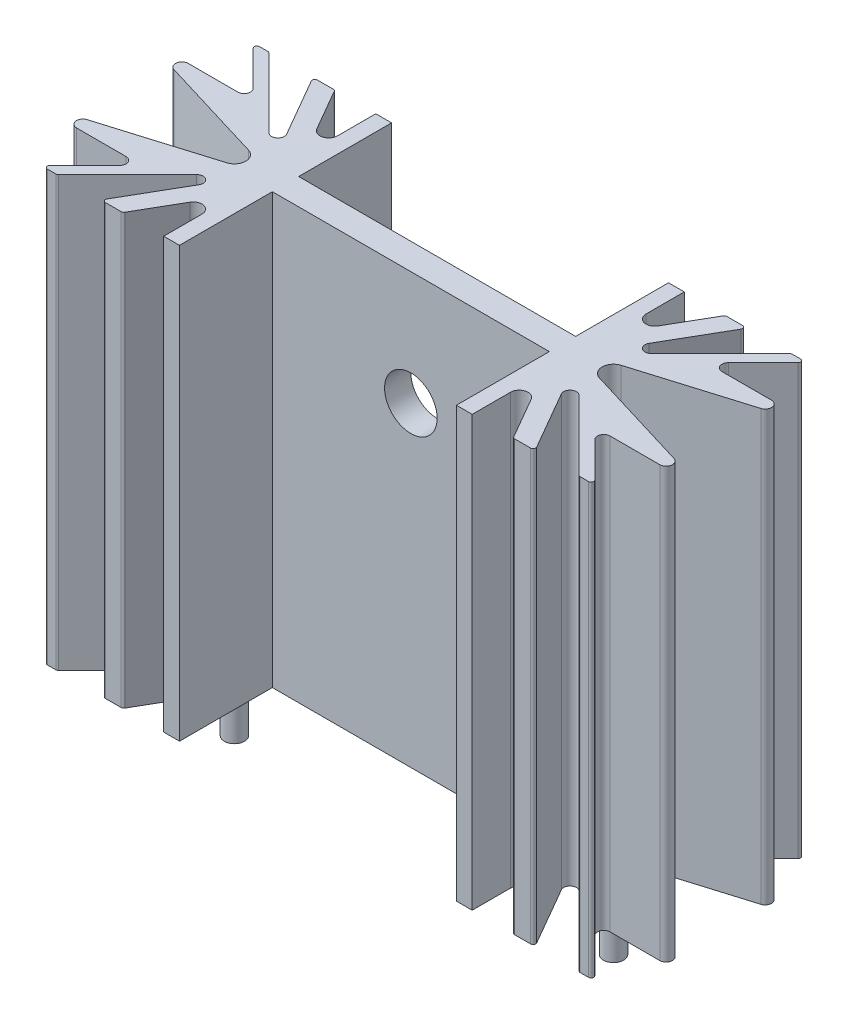
SolidWorks part; units mm, degrees
ref_plane "Front Plane" through (0, 0, 0) normal (0, 0, 1) x (1, 0, 0)
ref_plane "Top Plane" through (0, 0, 0) normal (0, 1, 0) x (1, 0, 0)
ref_plane "Right Plane" through (0, 0, 0) normal (1, 0, 0) x (0, 0, -1)
sketch "Sketch2" plane through (0, 0, 0) normal (0, 1, 0) x (1, 0, 0)
  line L0 (0, 16.6412) -> (0, -12.8924) construction
  line L1 (-22.8588, 0) -> (21.9444, 0) construction
  line L2 (-7.9, -0.75) -> (7.9, -0.75)
  line L3 (7.9, -0.75) -> (7.9, -6.05)
  line L4 (-7.9, -0.75) -> (-7.9, -6.05)
  line L5 (7.9, -6.05) -> (8.8, -6.05)
  line L6 (8.8, -6.05) -> (8.8, -3.866)
  line L7 (9.733, -3.616) -> (11.095, -5.975)
  line L8 (11.2249, -6.05) -> (12.1249, -6.05)
  line L9 (12.2548, -5.825) -> (10.3351, -2.5)
  line L10 (10.9063, -2.0617) -> (14.8507, -6.0061)
  line L11 (14.9568, -6.05) -> (15.4325, -6.05)
  line L12 (15.5386, -5.7939) -> (13.5509, -3.8063)
  line L13 (13.8077, -3.1864) -> (16.6369, -3.1864)
  line L14 (17, -2.8233) -> (17, -6.05) construction
  line L15 (16.7422, -2.4757) -> (10.625, -0.6221)
  line L16 (-7.9, -6.05) -> (-8.8, -6.05)
  line L17 (-8.8, -6.05) -> (-8.8, -3.866)
  line L18 (-9.733, -3.616) -> (-11.095, -5.975)
  line L19 (-11.2249, -6.05) -> (-12.1249, -6.05)
  line L20 (-12.2548, -5.825) -> (-10.3351, -2.5)
  line L21 (-10.9063, -2.0617) -> (-14.8507, -6.0061)
  line L22 (-14.9568, -6.05) -> (-15.4325, -6.05)
  line L23 (-15.5386, -5.7939) -> (-13.5509, -3.8063)
  line L24 (-13.8077, -3.1864) -> (-16.6369, -3.1864)
  line L25 (-16.7422, -2.4757) -> (-10.625, -0.6221)
  line L26 (17, 2.8233) -> (17, 6.05) construction
  line L27 (0, -16.6412) -> (0, 12.8924) construction
  line L28 (-16.7422, 2.4757) -> (-10.625, 0.6221)
  line L29 (-13.8077, 3.1864) -> (-16.6369, 3.1864)
  line L30 (-15.5386, 5.7939) -> (-13.5509, 3.8063)
  line L31 (-14.9568, 6.05) -> (-15.4325, 6.05)
  line L32 (-10.9063, 2.0617) -> (-14.8507, 6.0061)
  line L33 (-12.2548, 5.825) -> (-10.3351, 2.5)
  line L34 (-11.2249, 6.05) -> (-12.1249, 6.05)
  line L35 (-9.733, 3.616) -> (-11.095, 5.975)
  line L36 (-8.8, 6.05) -> (-8.8, 3.866)
  line L37 (-7.9, 6.05) -> (-8.8, 6.05)
  line L38 (16.7422, 2.4757) -> (10.625, 0.6221)
  line L39 (13.8077, 3.1864) -> (16.6369, 3.1864)
  line L40 (15.5386, 5.7939) -> (13.5509, 3.8063)
  line L41 (14.9568, 6.05) -> (15.4325, 6.05)
  line L42 (10.9063, 2.0617) -> (14.8507, 6.0061)
  line L43 (12.2548, 5.825) -> (10.3351, 2.5)
  line L44 (11.2249, 6.05) -> (12.1249, 6.05)
  line L45 (9.733, 3.616) -> (11.095, 5.975)
  line L46 (8.8, 6.05) -> (8.8, 3.866)
  line L47 (7.9, 6.05) -> (8.8, 6.05)
  line L48 (-7.9, 0.75) -> (-7.9, 6.05)
  line L49 (7.9, 0.75) -> (7.9, 6.05)
  line L50 (-7.9, 0.75) -> (7.9, 0.75)
  arc A0 (10.625, -0.6221) -> (10.625, 0.6221) centre (10.8135, 0) cw
  arc A1 (10.3351, -2.5) -> (10.9063, -2.0617) centre (10.6496, -2.3184) cw
  arc A2 (11.095, -5.975) -> (11.2249, -6.05) centre (11.2249, -5.9) ccw
  arc A3 (16.7422, -2.4757) -> (16.6369, -3.1864) centre (16.6369, -2.8233) cw
  arc A4 (13.8077, -3.1864) -> (13.5509, -3.8063) centre (13.8077, -3.5495) ccw
  arc A5 (9.733, -3.616) -> (8.8, -3.866) centre (9.3, -3.866) ccw
  arc A6 (12.1249, -6.05) -> (12.2548, -5.825) centre (12.1249, -5.9) ccw
  arc A7 (14.8507, -6.0061) -> (14.9568, -6.05) centre (14.9568, -5.9) ccw
  arc A8 (15.4325, -6.05) -> (15.5386, -5.7939) centre (15.4325, -5.9) ccw
  arc A9 (-9.733, -3.616) -> (-8.8, -3.866) centre (-9.3, -3.866) cw
  arc A10 (-11.095, -5.975) -> (-11.2249, -6.05) centre (-11.2249, -5.9) cw
  arc A11 (-12.1249, -6.05) -> (-12.2548, -5.825) centre (-12.1249, -5.9) cw
  arc A12 (-10.3351, -2.5) -> (-10.9063, -2.0617) centre (-10.6496, -2.3184) ccw
  arc A13 (-14.8507, -6.0061) -> (-14.9568, -6.05) centre (-14.9568, -5.9) cw
  arc A14 (-15.4325, -6.05) -> (-15.5386, -5.7939) centre (-15.4325, -5.9) cw
  arc A15 (-13.8077, -3.1864) -> (-13.5509, -3.8063) centre (-13.8077, -3.5495) cw
  arc A16 (-16.7422, -2.4757) -> (-16.6369, -3.1864) centre (-16.6369, -2.8233) ccw
  arc A17 (-16.7422, 2.4757) -> (-16.6369, 3.1864) centre (-16.6369, 2.8233) cw
  arc A18 (-13.8077, 3.1864) -> (-13.5509, 3.8063) centre (-13.8077, 3.5495) ccw
  arc A19 (-15.4325, 6.05) -> (-15.5386, 5.7939) centre (-15.4325, 5.9) ccw
  arc A20 (-14.8507, 6.0061) -> (-14.9568, 6.05) centre (-14.9568, 5.9) ccw
  arc A21 (-10.3351, 2.5) -> (-10.9063, 2.0617) centre (-10.6496, 2.3184) cw
  arc A22 (-12.1249, 6.05) -> (-12.2548, 5.825) centre (-12.1249, 5.9) ccw
  arc A23 (-11.095, 5.975) -> (-11.2249, 6.05) centre (-11.2249, 5.9) ccw
  arc A24 (-9.733, 3.616) -> (-8.8, 3.866) centre (-9.3, 3.866) ccw
  arc A25 (15.4325, 6.05) -> (15.5386, 5.7939) centre (15.4325, 5.9) cw
  arc A26 (14.8507, 6.0061) -> (14.9568, 6.05) centre (14.9568, 5.9) cw
  arc A27 (12.1249, 6.05) -> (12.2548, 5.825) centre (12.1249, 5.9) cw
  arc A28 (9.733, 3.616) -> (8.8, 3.866) centre (9.3, 3.866) cw
  arc A29 (13.8077, 3.1864) -> (13.5509, 3.8063) centre (13.8077, 3.5495) cw
  arc A30 (16.7422, 2.4757) -> (16.6369, 3.1864) centre (16.6369, 2.8233) ccw
  arc A31 (11.095, 5.975) -> (11.2249, 6.05) centre (11.2249, 5.9) cw
  arc A32 (10.3351, 2.5) -> (10.9063, 2.0617) centre (10.6496, 2.3184) ccw
  arc A33 (-10.625, -0.6221) -> (-10.625, 0.6221) centre (-10.8135, 0) ccw
  point P8 (0, -0.75)
  point P20 (16.4383, -1.1755)
  point P25 (0, 0)
  point P26 (10.8135, 0)
  point P27 (13.4613, -3.616)
  point P34 (14.8946, -6.05)
  point P42 (15.7946, -6.05)
  point P48 (8.8, -2)
  point P63 (-14.8946, -6.05)
  point P133 (-14.8946, 6.05)
  point P134 (8.8, 2)
  point P135 (15.7946, 6.05)
  point P136 (14.8946, 6.05)
  point P137 (0, 0.75)
  dimension "D7" = 0.65
  dimension "D8" = 45
  dimension "D10" = 17
  dimension "D13" = 0.5
  dimension "D12" = 0.15
  dimension "D1" = 15.8
  dimension "D2" = 1.5
  dimension "D3" = 5.3
  dimension "D4" = 0.9
  dimension "D5" = 4
  dimension "D6" = 30
  dimension "D9" = 0.9
  dimension "D11" = 0.5
extrude "Boss-Extrude1" add sketch "Sketch2" along normal mid plane 24.5
sketch "Sketch3" plane through (0, 0, 0.75) normal (0, 0, 1) x (1, 0, 0)
  line L0 (0, 7.25) -> (3.2045, 7.25) construction
  line L1 (-7.9, 12.25) -> (7.9, 12.25) construction
  circle A0 centre (0, 5.75) radius 1.5
  point P6 (0, 0)
  dimension "D1" = 5
  dimension "D2" = 3
extrude "Cut-Extrude1" cut sketch "Sketch3" against normal blind 24.5
sketch "Sketch4" plane through (0, -12.25, 0) normal (0, -1, 0) x (1, 0, 0)
  line L0 (0, 2.8743) -> (0, 0) construction
  circle A0 centre (-10.8135, 0) radius 0.575
  circle A1 centre (10.8135, 0) radius 0.575
  dimension "D1" = 1.15
extrude "Boss-Extrude2" add sketch "Sketch4" along normal blind 4.2 and the other way blind 6 separate body
